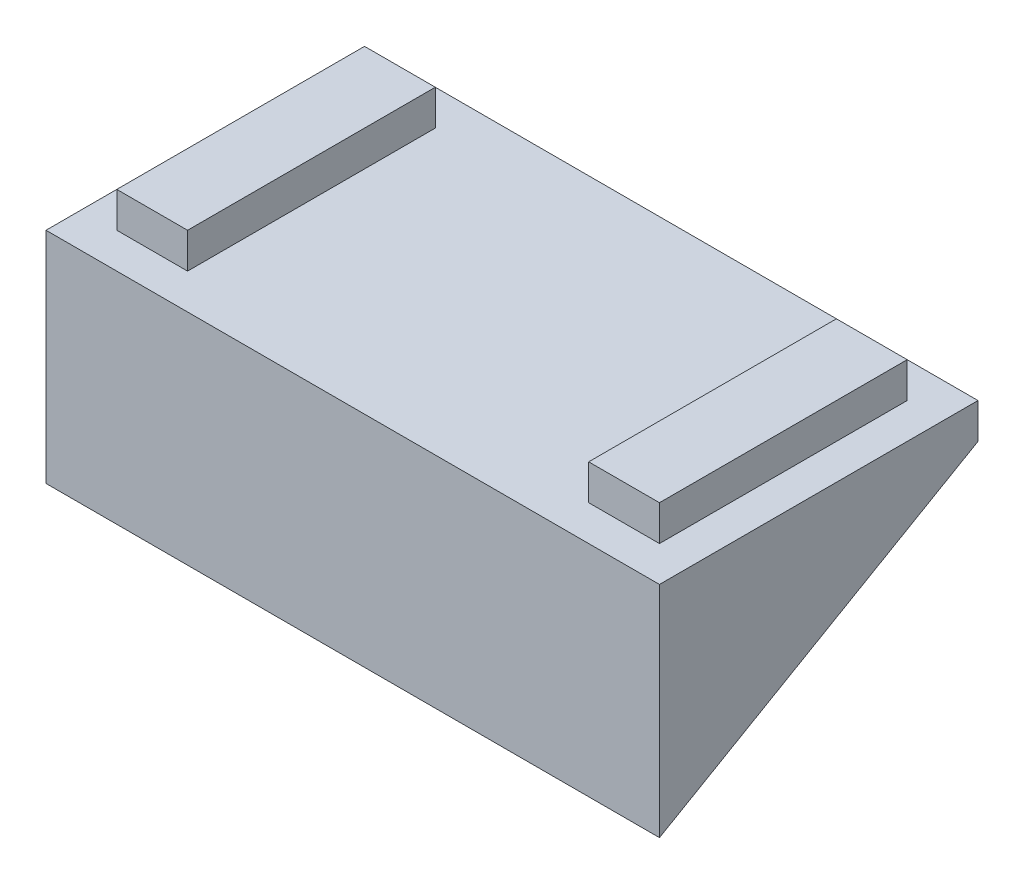
SolidWorks part; units mm, degrees
ref_plane "Front Plane" through (0, 0, 0) normal (0, 0, 1) x (1, 0, 0)
ref_plane "Top Plane" through (0, 0, 0) normal (0, 1, 0) x (1, 0, 0)
ref_plane "Right Plane" through (0, 0, 0) normal (1, 0, 0) x (0, 0, -1)
sketch "Sketch1" plane through (0, 0, 0) normal (0, 1, 0) x (1, 0, 0)
  line L1 (-23, -10.5) -> (23, -10.5)
  line L2 (-23, -10.5) -> (-23, 10.5)
  line L3 (-23, 10.5) -> (23, 10.5)
  line L4 (23, -10.5) -> (23, 10.5)
  line L5 (-23, -10.5) -> (23, 10.5) construction
  line L6 (-23, 10.5) -> (23, -10.5) construction
  line L7 (17, 10.5) -> (23, 10.5)
  line L8 (17, 10.5) -> (17, -10.5)
  line L9 (17, -10.5) -> (23, -10.5)
  line L10 (23, 10.5) -> (23, -10.5)
  line L11 (-23, 10.5) -> (-17, 10.5)
  line L12 (-23, 10.5) -> (-23, -10.5)
  line L13 (-23, -10.5) -> (-17, -10.5)
  line L14 (-17, 10.5) -> (-17, -10.5)
  line L15 (-26, 13.5) -> (26, 13.5)
  line L16 (-26, 13.5) -> (-26, -13.5)
  line L17 (-26, -13.5) -> (26, -13.5)
  line L18 (26, 13.5) -> (26, -13.5)
  point P0 (0, 0)
  dimension "D1" = 46
  dimension "D2" = 21
  dimension "D3" = 6
  dimension "D4" = 6
  dimension "D5" = 3
  dimension "D6" = 3
  dimension "D7" = 3
  dimension "D8" = 3
extrude "Boss-Extrude1" add sketch "Sketch1" along normal blind 3 contours L14 L3 L2 L1 | L3 L8 L1 L4 region at (-20, 0, 0) region at (20, 0, 0)
extrude "Boss-Extrude2" add sketch "Sketch1<3>" against normal blind 3 separate body contours L18 L15 L16 L17 L4 L1 L2 L3 | L3 L14 L1 L8 | L14 L3 L2 L1 | L3 L8 L1 L4 region at (-20, 0, 0) region at (0, 0, 0) region at (20, 0, 0) region at (0, 0, -12.9141)
sketch "Sketch1<3>" plane through (0, 0, 0) normal (0, 1, 0) x (1, 0, 0) same geometry as "Sketch1"
sketch "Sketch2" plane through (-26, 0, 0) normal (-1, 0, 0) x (0, 0, 1)
  line L0 (13.5, -3) -> (13.5, -18.5885)
  line L1 (13.5, -18.5885) -> (-13.5, -3)
  line L2 (-13.5, -3) -> (13.5, -3) construction
  line L7 (13.5, 0) -> (-13.5, 0)
  line L8 (-13.5, 0) -> (-13.5, -3)
  line L9 (-13.5, -3) -> (13.5, -3)
  line L10 (13.5, -3) -> (13.5, 0)
  line L11 (13.5, 0) -> (-13.5, 0)
  line L12 (-13.5, 0) -> (-13.5, -3)
  line L14 (13.5, -3) -> (13.5, 0)
  dimension "D1" = 30
  dimension "D2" = 0
extrude "Boss-Extrude3" add sketch "Sketch2" against normal blind 52
